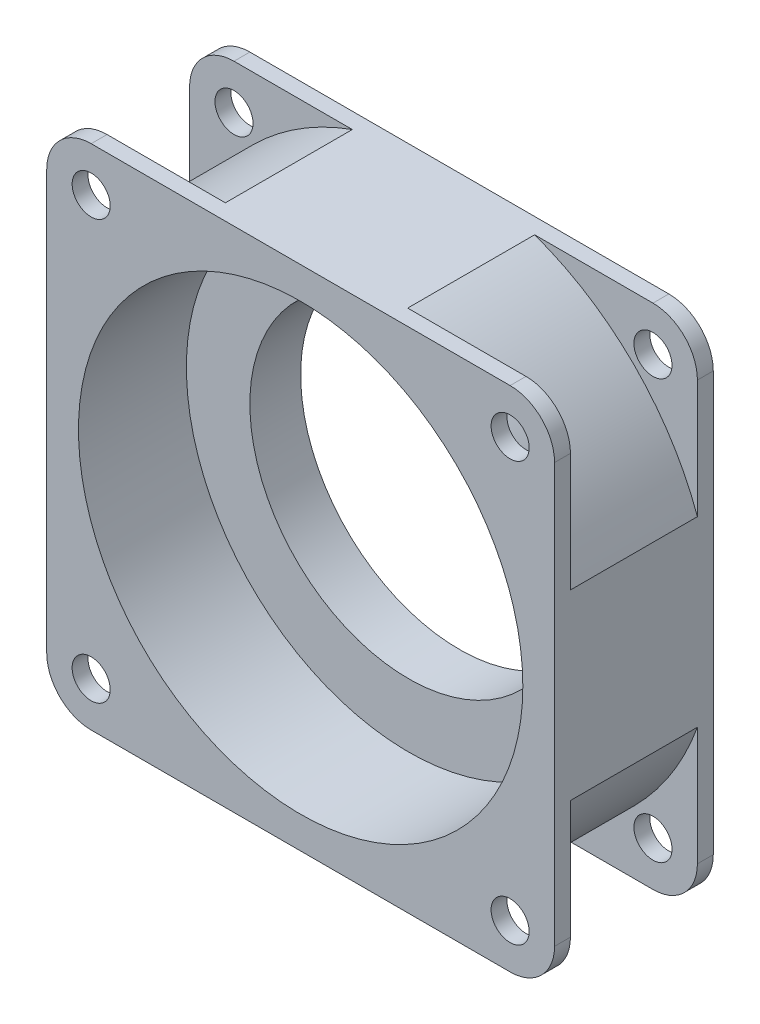
SolidWorks part; units mm, degrees
ref_plane "Front Plane" through (0, 0, 0) normal (0, 0, 1) x (1, 0, 0)
ref_plane "Top Plane" through (0, 0, 0) normal (0, 1, 0) x (1, 0, 0)
ref_plane "Right Plane" through (0, 0, 0) normal (1, 0, 0) x (0, 0, -1)
sketch "Sketch1" plane through (0, 0, 0) normal (0, 0, 1) x (1, 0, 0)
  line L0 (0, 4.9306) -> (0, -6.1806) construction
  line L1 (-33, -40) -> (33, -40)
  line L2 (-40, -33) -> (-40, 33)
  line L3 (-33, 40) -> (33, 40)
  line L4 (40, -33) -> (40, 33)
  line L5 (-40, -40) -> (40, 40) construction
  line L6 (-40, 40) -> (40, -40) construction
  line L7 (5.9722, 0) -> (-5.8333, 0) construction
  arc A0 (40, 14.3614) -> (14.3614, 40) centre (0, 0) ccw
  circle A1 centre (0, 0) radius 35
  circle A2 centre (0, 0) radius 25
  arc A3 (-40, -14.3614) -> (-14.3614, -40) centre (0, 0) ccw
  arc A4 (-14.3614, 40) -> (-40, 14.3614) centre (0, 0) ccw
  arc A5 (14.3614, -40) -> (40, -14.3614) centre (0, 0) ccw
  arc A6 (-40, 33) -> (-33, 40) centre (-33, 33) cw
  arc A7 (-33, -40) -> (-40, -33) centre (-33, -33) cw
  arc A8 (33, -40) -> (40, -33) centre (33, -33) ccw
  arc A9 (33, 40) -> (40, 33) centre (33, 33) cw
  circle A10 centre (-33, 33) radius 3
  circle A11 centre (33, 33) radius 3
  circle A12 centre (-33, -33) radius 3
  circle A13 centre (33, -33) radius 3
  dimension "D3" = 50
  dimension "D4" = 70
  dimension "D5" = 85
  dimension "D6" = 7
  dimension "D7" = 6
  dimension "D1" = 80
  dimension "D2" = 80
extrude "Boss-Extrude1" add sketch "Sketch1" along normal blind 2.5 from offset 10 contours A9 L3 A0 L4 A11 | A6 L2 A4 L3 A10 | A7 L1 A3 L2 A12 | L1 A8 L4 A5 A13 region at (-37.6934, -37.6934, 0) region at (30.3084, -30.3084, 0) region at (-39.6374, 23.6807, 0) region at (30.3084, 30.3084, 0)
extrude "Boss-Extrude2" add sketch "Sketch1<3>" along normal mid plane 25 contours L1 A5 L4 A0 L3 A4 L2 A3 A1 region at (-29.252, -29.252, 0)
sketch "Sketch1<3>" plane through (0, 0, 0) normal (0, 0, 1) x (1, 0, 0) same geometry as "Sketch1"
mirror "Mirror1" about plane through (0, 0, 0) normal (0, 0, 1) of "Boss-Extrude1"
extrude "Boss-Extrude4" add sketch "Sketch1<5>" against normal blind 8 from offset 4.5 contours A1 A2 | L1 A5 L4 A0 L3 A4 L2 A3 A1 region at (-29.252, -29.252, 0) region at (-34.0101, 0, 0) offset against normal yes
sketch "Sketch1<5>" plane through (0, 0, 0) normal (0, 0, 1) x (1, 0, 0) same geometry as "Sketch1"
